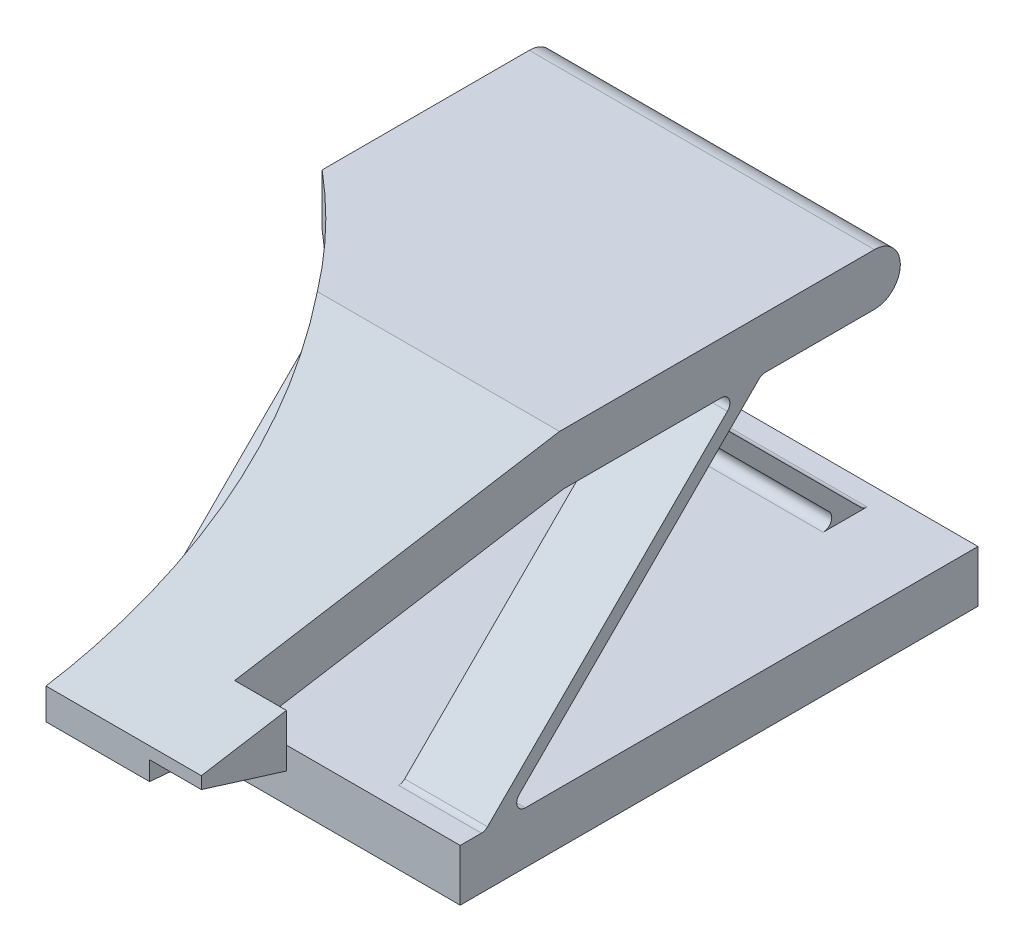
SolidWorks part; units mm, degrees
material "ABS"
ref_plane "Front" through (0, 0, 0) normal (0, 0, 1) x (1, 0, 0)
ref_plane "Top" through (0, 0, 0) normal (0, 1, 0) x (1, 0, 0)
ref_plane "Right" through (0, 0, 0) normal (1, 0, 0) x (0, 0, -1)
ref_axis "X" through (-80.9, 0, 0) along (1, 0, 0)
ref_axis "Y" through (0, -50, 0) along (0, 1, 0)
ref_axis "Z" through (0, 0, -80.9) along (0, 0, 1)
sketch "Sketch1" plane through (0, 0, 0) normal (1, 0, 0) x (0, 0, -1)
  line L0 (0, 13) -> (0, 11.2)
  line L1 (0, 11.2) -> (4.9304, 10.7686)
  line L4 (0, 0) -> (0, -4) construction
  line L5 (0, -4) -> (30.1272, -4) construction
  line L6 (18, -4) -> (48, -4)
  line L7 (48, -4) -> (48, -1)
  line L9 (18, -1) -> (18, -4)
  line L11 (24, 13.8967) -> (42, 13.8967)
  line L13 (42, 16.8967) -> (23.7556, 16.8967)
  line L14 (33, 13.8967) -> (33, -1) construction
  line L15 (31.1033, 13.8967) -> (46, -1) construction
  line L16 (34.8967, 13.8967) -> (20, -1) construction
  line L17 (46, -1) -> (33, -1) construction
  line L18 (33, -1) -> (20, -1) construction
  line L19 (18, -1) -> (48, -1)
  line L20 (0, 13) -> (23.7556, 16.8967)
  line L21 (24, 13.8967) -> (4.9304, 10.7686)
  line L22 (24, 13.8967) -> (23.5144, 16.8571) construction
  line L24 (42, 16.8967) -> (42, 13.8967) construction
  circle A0 centre (0, 0) radius 13 construction
  circle A1 centre (0, 0) radius 1.5 construction
  arc A2 (42, 16.8967) -> (42, 13.8967) centre (42, 15.3967) cw
  point P24 (33, 12)
  point P29 (18, -2.5)
  dimension "D1" = 26
  dimension "D4" = 3
  dimension "D2" = 1.8
  dimension "D3" = 5
  dimension "D5" = 4
  dimension "D6" = 3
  dimension "D8" = 2
  dimension "D9" = 18.3848
  dimension "D7" = 21.0671
  dimension "D10" = 9
  dimension "D11" = 3
  dimension "D12" = 18
extrude "Boss-Extrude1" add sketch "Sketch1" along normal mid plane 20
sketch "Sketch2" plane through (0, 0, 0) normal (1, 0, 0) x (0, 0, -1)
  line L0 (31.1033, 13.8967) -> (46, -1) construction
  line L1 (30.5376, 13.8967) -> (45.4343, -1)
  line L2 (31.669, 13.8967) -> (46.5657, -1)
  line L3 (18, -1) -> (48, -1) construction
  line L4 (24, 13.8967) -> (42, 13.8967) construction
  line L5 (45.4343, -1) -> (46.5657, -1)
  line L6 (30.5376, 13.8967) -> (31.669, 13.8967)
  line L7 (31.3862, 14.1795) -> (46.2828, -0.7172) construction
  line L8 (30.8205, 13.6138) -> (45.7172, -1.2828) construction
  dimension "D1" = 0.4
  dimension "D2" = 0.4
extrude "Boss-Extrude2" add sketch "Sketch2" along normal mid plane 9.6
sketch "Sketch3" plane through (0, 0, 0) normal (1, 0, 0) x (0, 0, -1)
  line L0 (34.8967, 13.8967) -> (20, -1) construction
  line L1 (18, -1) -> (48, -1) construction
  line L2 (24, 13.8967) -> (42, 13.8967) construction
  line L3 (19.4343, -1) -> (20.5657, -1)
  line L4 (34.331, 13.8967) -> (35.4624, 13.8967)
  line L5 (34.331, 13.8967) -> (19.4343, -1)
  line L6 (35.4624, 13.8967) -> (20.5657, -1)
  line L7 (35.1795, 13.6138) -> (20.2828, -1.2828) construction
  line L8 (34.6138, 14.1795) -> (19.7172, -0.7172) construction
  dimension "D1" = 0.4
  dimension "D2" = 0.4
extrude "Boss-Extrude3" add sketch "Sketch3" along normal blind 4.8 from offset 5.2
mirror "Mirror1" about plane through (0, 0, 0) normal (1, 0, 0) of "Boss-Extrude3"
fillet "Fillet1" radius 0.5 10 edges at (-7.6, -1, -20.5657) (-7.6, -1, -19.4343) (7.6, -1, -19.4343) (7.6, -1, -20.5657) (0, -1, -45.4343) (0, -1, -46.5657) (0, 13.8967, -31.669) (0, 13.8967, -30.5376) (7.6, 13.8967, -34.331) (7.6, 13.8967, -35.4624)
sketch "Sketch4" plane through (0, 16.8967, 0) normal (0, 1, 0) x (1, 0, 0)
  line L1 (10, 0) -> (-10, 0) construction
  line L2 (-10, 42) -> (-10, 23.7556) construction
  line L3 (-10, 30) -> (-10, 0)
  line L4 (-10, 0) -> (-3, 0)
  line L5 (3, 0) -> (10, 0)
  line L6 (10, 0) -> (10, 30)
  line L7 (10, 42) -> (10, 23.7556) construction
  line L9 (0, 0) -> (0, 50.5606) construction
  line L10 (3, 0) -> (3, -3.0723) construction
  arc A0 (3, 0) -> (10, 30) centre (70.7857, 0) cw
  arc A1 (-3, 0) -> (-10, 30) centre (-70.7857, 0) ccw
  dimension "D1" = 6
  dimension "D2" = 30
extrude "Cut-Extrude1" [suppressed] cut sketch "Sketch4" against normal up to next
sketch "Sketch5" plane through (0, 16.8967, 0) normal (0, 1, 0) x (1, 0, 0)
  line L0 (-10, 0) -> (-10, 30)
  line L1 (-10, 42) -> (-10, 23.7556) construction
  line L2 (10, 0) -> (-10, 0) construction
  line L3 (4, 0) -> (-10, 0)
  line L4 (4, 0) -> (4, -1.1619) construction
  line L5 (10, 23.7556) -> (10, 0) construction
  arc A1 (4, 0) -> (-10, 30) centre (-35.1429, 0) ccw
  dimension "D1" = 6
  dimension "D2" = 30
extrude "Cut-Extrude2" cut sketch "Sketch5" against normal up to next
sketch "Sketch6" plane through (10, 0, 0) normal (1, 0, 0) x (0, 0, -1)
  line L0 (0, 13) -> (4.9304, 13.8087)
  line L1 (4.9304, 13.8087) -> (4.9304, 10.7686)
  line L2 (4.9304, 10.7686) -> (0, 12.3)
  line L3 (0, 13) -> (0, 11.2) construction
  line L4 (0, 12.3) -> (0, 13)
  line L5 (23.7556, 16.8967) -> (0, 13) construction
  point P10 (0, 12.3896)
  dimension "D1" = 0.7
extrude "Boss-Extrude4" add sketch "Sketch6" along normal blind 3
equation "\"D7@Sketch1\"= \"D9@Sketch1\" / ( 0.5 + sqr ( 5 ) / 6 )"
